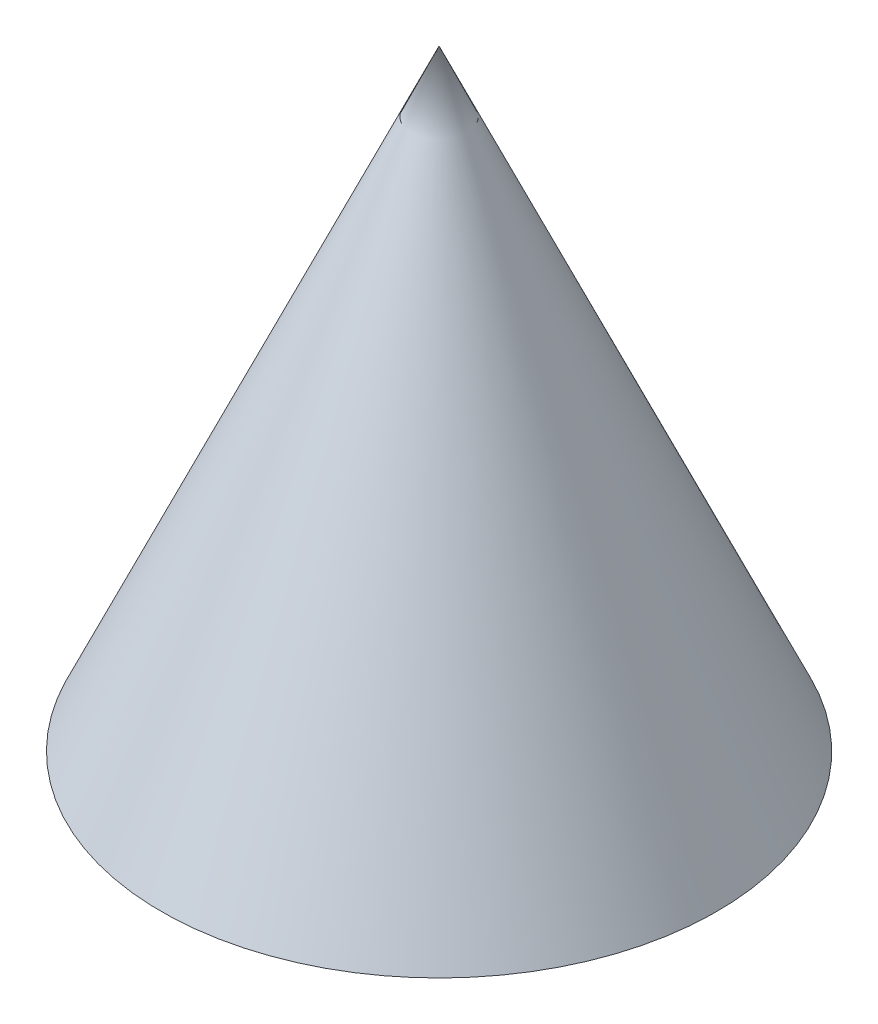
SolidWorks part; units mm, degrees
ref_plane "前视基准面" through (0, 0, 0) normal (0, 0, 1) x (1, 0, 0)
ref_plane "上视基准面" through (0, 0, 0) normal (0, 1, 0) x (1, 0, 0)
ref_plane "右视基准面" through (0, 0, 0) normal (1, 0, 0) x (0, 0, -1)
sketch "草图1" plane through (0, 0, 0) normal (0, 0, 1) x (1, 0, 0)
  line L0 (0, 110) -> (50, 0)
  line L1 (50, 0) -> (0, 0)
  line L2 (0, 0) -> (0, 110) construction
  line L3 (0, 110) -> (0, 0)
  dimension "R" = 50
  dimension "H" = 110
revolve "旋转1" add sketch "草图1" angle 360 about L2
shell "抽壳1" thickness 1 removed face at (0, 0, -50)
